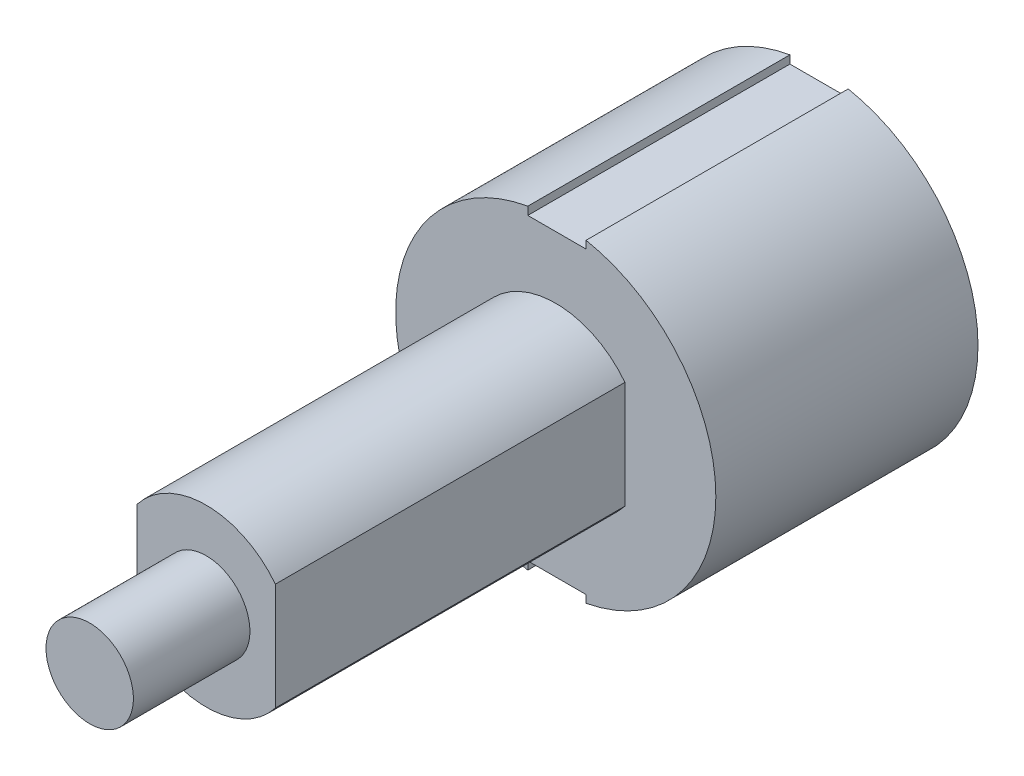
SolidWorks part; units mm, degrees
ref_plane "Alzado" through (0, 0, 0) normal (0, 0, 1) x (1, 0, 0)
ref_plane "Planta" through (0, 0, 0) normal (0, 1, 0) x (1, 0, 0)
ref_plane "Vista lateral" through (0, 0, 0) normal (1, 0, 0) x (0, 0, -1)
sketch "Croquis1" plane through (0, 0, 0) normal (0, 0, 1) x (1, 0, 0)
  line L0 (0, 0) -> (0, 2.3812) construction
  line L1 (0, 0) -> (12.8492, 0) construction
  line L2 (0, 4.7701) -> (0, 11.4337) construction
  line L4 (-1.524, 8.5908) -> (-1.524, 8.1527)
  line L5 (-1.524, 8.1527) -> (1.651, 8.1527)
  line L6 (1.651, 8.5673) -> (1.651, 8.1527)
  line L8 (-3.7706, -2.9217) -> (-3.7706, 2.9217)
  line L10 (3.7706, -2.9217) -> (3.7706, 2.9217)
  line L11 (1.651, -8.5673) -> (1.651, -8.1527)
  line L12 (-1.524, -8.1527) -> (1.651, -8.1527)
  line L13 (-1.524, -8.5908) -> (-1.524, -8.1527)
  arc A0 (-1.524, 8.5908) -> (-1.524, -8.5908) centre (0, 0) ccw
  arc A1 (-3.7706, -2.9217) -> (3.7706, -2.9217) centre (0, 0) ccw
  circle A2 centre (0, 0) radius 2.3813
  arc A3 (3.7706, 2.9217) -> (-3.7706, 2.9217) centre (0, 0) ccw
  arc A4 (-1.524, -8.5908) -> (-1.524, 8.5908) centre (0, 0) cw
  arc A5 (1.651, -8.5673) -> (1.651, 8.5673) centre (0, 0) ccw
  arc A6 (1.651, 8.5673) -> (1.651, -8.5673) centre (0, 0) cw
  point P9 (0, 8.7249)
  dimension "D1" = 17.4498
  dimension "D2" = 4.7701
  dimension "D3" = 4.7625
  dimension "D4" = 3.175
  dimension "D5" = 1.524
  dimension "D6" = 8.1527
  dimension "D7" = 7.5413
  dimension "D8" = 3.7706
extrude "Saliente-Extruir4" add sketch "Croquis1" along normal blind 14.2875 contours L11 A5 L6 L5 L4 A0 L13 L12 A3 L10 A1 L8 region at (-1.7689, 8.3717, 0)
extrude "Saliente-Extruir5" add sketch "Croquis1<6>" along normal blind 33.3375 contours L10 A3 L8 A1 A2 region at (-3.649, 0, 0)
sketch "Croquis1<6>" plane through (0, 0, 0) normal (0, 0, 1) x (1, 0, 0) same geometry as "Croquis1"
extrude "Saliente-Extruir6" add sketch "Croquis1<7>" along normal blind 39.6875 contours A2 region at (0, 0, 0)
sketch "Croquis1<7>" plane through (0, 0, 0) normal (0, 0, 1) x (1, 0, 0) same geometry as "Croquis1"
